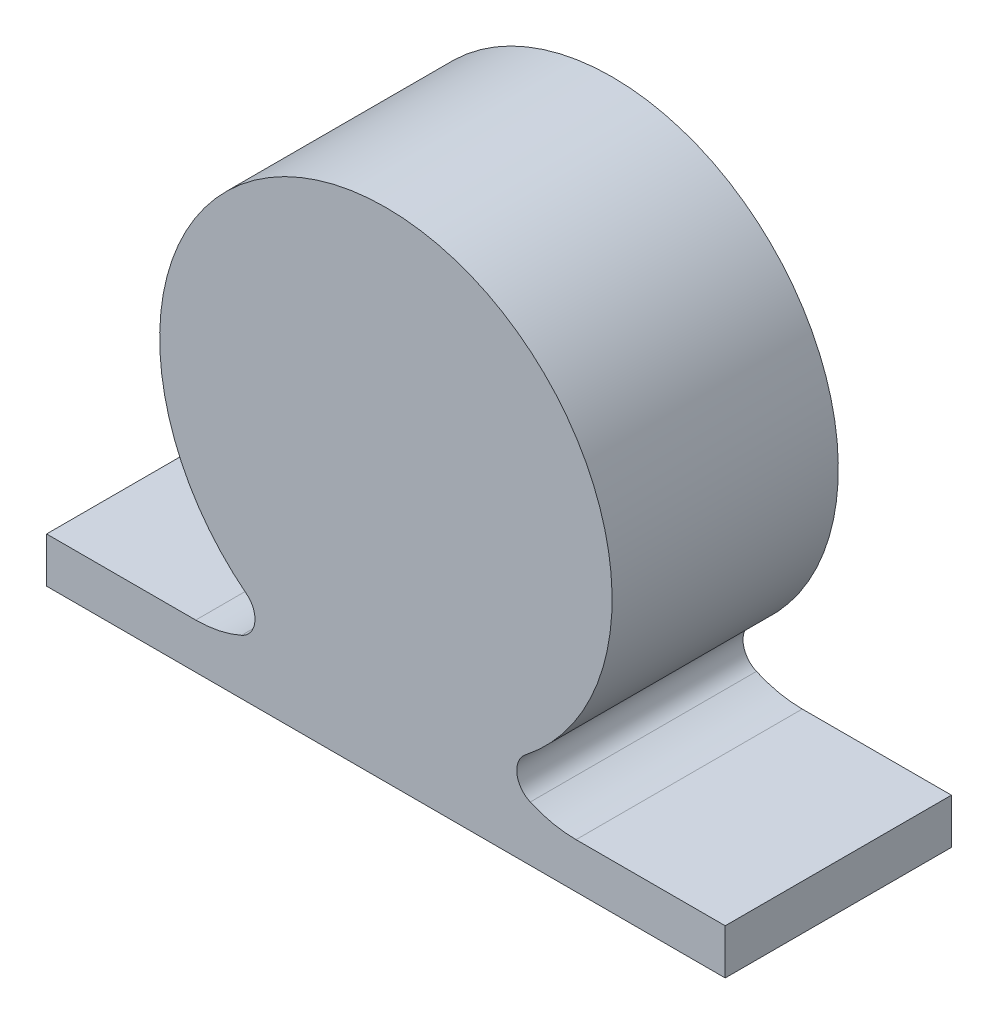
SolidWorks part; units mm, degrees
material "ABS"
ref_plane "Front Plane" through (0, 0, 0) normal (0, 0, 1) x (1, 0, 0)
ref_plane "Top Plane" through (0, 0, 0) normal (0, 1, 0) x (1, 0, 0)
ref_plane "Right Plane" through (0, 0, 0) normal (1, 0, 0) x (0, 0, -1)
sketch "Sketch1" plane through (0, 0, 0) normal (0, 0, 1) x (1, 0, 0)
  line L1 (-2.54, -1.651) -> (2.54, -1.651)
  line L2 (-2.54, -1.651) -> (-2.54, -6.096)
  line L3 (-2.54, -6.096) -> (2.54, -6.096)
  line L4 (2.54, -1.651) -> (2.54, -6.096)
  line L5 (0, -5.08) -> (7.62, -5.08)
  line L6 (0, -5.08) -> (0, -6.096)
  line L7 (0, -6.096) -> (7.62, -6.096)
  line L8 (7.62, -5.08) -> (7.62, -6.096)
  line L9 (0, -5.08) -> (-7.62, -5.08)
  line L10 (0, -5.08) -> (0, -6.096)
  line L11 (0, -6.096) -> (-7.62, -6.096)
  line L12 (-7.62, -5.08) -> (-7.62, -6.096)
  circle A0 centre (0, 0) radius 5.08
  dimension "D1" = 10.16
  dimension "D2" = 5.08
  dimension "D3" = 2.54
  dimension "D4" = 4.445
  dimension "D5" = 7.62
  dimension "D6" = 7.62
  dimension "D7" = 1.016
  dimension "D8" = 0
extrude "Boss-Extrude1" add sketch "Sketch1" along normal blind 5.08 contours L4 A0 L2 L1 | L2 A0 L4 L1 | A0 L2 L9 | A0 L5 L4 | L5 L6 L3 L4 | L9 L12 L11 L2 | L8 L5 L4 L7 | L6 L9 L2 L3 region at (0, 0.8207, 0) region at (0, -3.2616, 0) region at (-1.9138, -4.8784, 0) region at (1.9138, -4.8784, 0) region at (-1.27, -5.588, 0) region at (-5.08, -5.588, 0) region at (1.27, -5.588, 0) region at (5.08, -5.588, 0)
fillet "Fillet1" radius 2.54 2 edges at (-2.54, -5.08, 2.54) (2.54, -5.08, 2.54)
fillet "Fillet2" radius 0.508 2 edges at (-2.54, -4.3994, 2.54) (2.54, -4.3994, 2.54)
